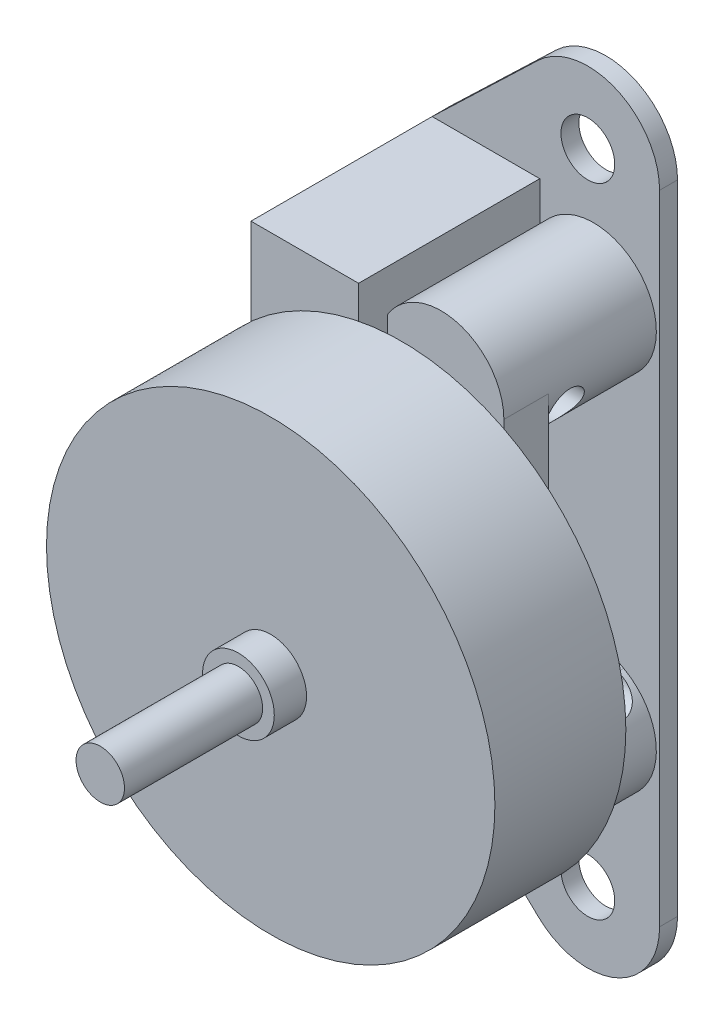
SolidWorks part; units mm, degrees
ref_plane "Front Plane" through (0, 0, 0) normal (0, 0, 1) x (1, 0, 0)
ref_plane "Top Plane" through (0, 0, 0) normal (0, 1, 0) x (1, 0, 0)
ref_plane "Right Plane" through (0, 0, 0) normal (1, 0, 0) x (0, 0, -1)
sketch "Sketch1" plane through (0, 0, 0) normal (0, 0, 1) x (1, 0, 0)
  line L0 (47.18, 17.78) -> (47.18, -17.78)
  line L1 (39.18, 17.78) -> (39.18, -17.78)
  circle A0 centre (43.18, 17.78) radius 1.5 construction
  circle A1 centre (43.18, 17.78) radius 1.5
  circle A2 centre (43.18, -17.78) radius 1.5 construction
  circle A3 centre (43.18, -17.78) radius 1.5
  circle A4 centre (43.18, 17.78) radius 4
  circle A5 centre (43.18, -17.78) radius 4
  point P12 (47.18, -17.78)
  dimension "D1" = 8
extrude "Boss-Extrude1" add sketch "Sketch1" along normal blind 1 contours A5 L0 A4 L1 | A4 A1 | A5 A3 region at (43.18, 13.8931, 0) region at (43.18, 0, 0) region at (43.18, -21.6669, 0)
sketch "Sketch2" plane through (0, 0, 1) normal (0, 0, 1) x (1, 0, 0)
  line L0 (40.4119, 20.6675) -> (34.5, 15)
  line L1 (34.5, 15) -> (34.5, -15)
  line L2 (34.5, -15) -> (40.4119, -20.6675)
  line L3 (39.18, 17.78) -> (39.18, -17.78) construction
  line L4 (39.18, 17.78) -> (39.18, -17.78)
  line L5 (48.5, -24.75) -> (48.5, 24.75) construction
  line L7 (34.5, 0) -> (39.18, 0) construction
  arc A0 (47.18, 17.78) -> (39.18, 17.78) centre (43.18, 17.78) ccw construction
  arc A1 (39.18, -17.78) -> (47.18, -17.78) centre (43.18, -17.78) ccw construction
  arc A2 (47.18, 17.78) -> (39.18, 17.78) centre (43.18, 17.78) ccw
  arc A3 (39.18, -17.78) -> (47.18, -17.78) centre (43.18, -17.78) ccw
  line M1 (39.18, 17.78) -> (39.18, -17.78)
  arc M2 (39.18, -17.78) -> (47.18, -17.78) centre (43.18, -17.78) ccw
  arc M4 (47.18, 17.78) -> (39.18, 17.78) centre (43.18, 17.78) ccw
  dimension "D1" = 14
  dimension "D2" = 30
extrude "Boss-Extrude2" add sketch "Sketch2" against normal blind 1 contours L1 L7 L0 M1 M4 | L7 L1 L2 L4 M2 region at (36.953, 8.7197, 1) region at (36.953, -8.7197, 1)
sketch "Sketch3" plane through (0, 0, 1) normal (0, 0, 1) x (1, 0, 0)
  line L0 (34.5, 15) -> (34.5, 11.5) construction
  line L1 (34.5, 15) -> (40.5, 15)
  line L2 (34.5, 15) -> (34.5, 6.75)
  line L3 (34.5, 6.75) -> (40.5, 6.75)
  line L4 (40.5, 15) -> (40.5, 6.75)
  line L5 (34.5, -15) -> (40.5, -15)
  line L6 (34.5, -15) -> (34.5, -3.75)
  line L7 (34.5, -3.75) -> (40.5, -3.75)
  line L8 (40.5, -15) -> (40.5, -3.75)
  line L9 (34.5, 11.5) -> (59.3702, 11.5) construction
  line L10 (34.5, -15) -> (34.5, -11.5) construction
  line L11 (34.5, -11.5) -> (58.5732, -11.5) construction
  line L12 (43.18, 17.78) -> (43.18, 11.5) construction
  line L13 (43.18, -17.78) -> (43.18, -11.5) construction
  dimension "D1" = 10.5
  dimension "D2" = 23
  dimension "D3" = 7.75
  dimension "D4" = 4.75
  dimension "D5" = 6
extrude "Boss-Extrude3" add sketch "Sketch3" along normal blind 7.1
sketch "Sketch4" plane through (0, 0, 1) normal (0, 0, 1) x (1, 0, 0)
  line L0 (37.5, 6.75) -> (37.5, -3.75) construction
  line L1 (34.5, 6.75) -> (40.5, 6.75) construction
  line L2 (40.5, -3.75) -> (34.5, -3.75) construction
  line L3 (37.5, 1.5) -> (43.5, 1.5) construction
  line L4 (34.5, 6.75) -> (34.5, -3.75) construction
  line L5 (40.5, 10.875) -> (56.47, 10.875) construction
  line L6 (40.5, 6.75) -> (40.5, 15) construction
  line L7 (40.5, -9.375) -> (56.47, -9.375) construction
  line L8 (40.5, -15) -> (40.5, -3.75) construction
  line L9 (43.5, 1.5) -> (43.5, -9.375) construction
  line L10 (43.5, 1.5) -> (43.5, 10.875) construction
  circle A0 centre (43.5, 1.5) radius 2.1
  circle A1 centre (43.5, 10.875) radius 3.5
  circle A2 centre (43.5, -9.375) radius 3.5
  line M3 (40.5, -3.75) -> (40.5, -15)
  line M11 (40.5, 15) -> (40.5, 6.75)
  dimension "D2" = 4.2
  dimension "D3" = 7
  dimension "D1" = 9
extrude "Boss-Extrude4" add sketch "Sketch4" along normal blind 6 contours A1 M11 | A2 M3 region at (43.6048, 10.875, 1) region at (43.6048, -9.375, 1)
sketch "Sketch5" plane through (0, 0, 7) normal (0, 0, 1) x (1, 0, 0)
  line L0 (47, 10.875) -> (47, -9.375)
  line L1 (40, 10.875) -> (40, -9.375)
  arc A0 (40.5, 9.0722) -> (40.5, 12.6778) centre (43.5, 10.875) ccw construction
  circle A1 centre (43.5, 10.875) radius 3.5
  arc A2 (40.5, -11.1778) -> (40.5, -7.5722) centre (43.5, -9.375) ccw construction
  circle A3 centre (43.5, -9.375) radius 3.5
  line M3 (40.5, 12.6778) -> (40.5, 9.0722)
  arc M4 (40.5, 9.0722) -> (40.5, 12.6778) centre (43.5, 10.875) ccw
extrude "Boss-Extrude5" add sketch "Sketch5" along normal blind 1.5 contours M4 M3 | A3 L0 A1 L1 M4 | A3 region at (43.6048, 10.875, 7) region at (43.5, 0.75, 7) region at (43.5, -9.375, 7)
extrude "Cut-Extrude1" cut sketch "Sketch4<3>" along normal blind 12 contours A0 region at (43.5, 1.5, 1)
sketch "Sketch4<3>" plane through (0, 0, 1) normal (0, 0, 1) x (1, 0, 0) same geometry as "Sketch4"
sketch "Sketch6" plane through (34.5, 0, 0) normal (-1, 0, 0) x (0, 0, 1)
  line L0 (8.1, 15) -> (8.1, 6.75) construction
  line L1 (8.1, 11.5) -> (0, 11.5) construction
  line L2 (8.1, 11.5) -> (8.1, -11.5) construction
  line L3 (8.1, -11.5) -> (0, -11.5) construction
  line L4 (0, 11.5) -> (0, -11.5) construction
  line L5 (0, 15) -> (0, -15) construction
  line L6 (8.1, -3.75) -> (8.1, -15) construction
  line L8 (0, 0) -> (8.1, 0) construction
  circle A0 centre (5.8, 9.5) radius 1
  circle A1 centre (2.3, -6.5) radius 1
  point P8 (0, 0)
  dimension "D2" = 16
  dimension "D3" = 2
  dimension "D1" = 23
  dimension "D4" = 2.3
  dimension "D5" = 2.3
  dimension "D6" = 2
  dimension "D7" = 5
extrude "Cut-Extrude2" cut sketch "Sketch6" against normal blind 13
sketch "Sketch7" plane through (0, 0, 8.5) normal (0, 0, 1) x (1, 0, 0)
  circle A0 centre (43.5, 1.5) radius 3.7
  dimension "D1" = 7.4
extrude "Boss-Extrude6" add sketch "Sketch7" along normal blind 3.2 separate body
sketch "Sketch8" plane through (0, 0, 11.7) normal (0, 0, 1) x (1, 0, 0)
  circle A0 centre (43.5, 1.5) radius 12.5
  dimension "D1" = 25
extrude "Boss-Extrude7" add sketch "Sketch8" along normal blind 7.3
sketch "Sketch9" plane through (0, 0, 19) normal (0, 0, 1) x (1, 0, 0)
  circle A0 centre (43.5, 1.5) radius 2
  dimension "D1" = 4
extrude "Boss-Extrude8" add sketch "Sketch9" along normal blind 1.8
sketch "Sketch10" plane through (0, 0, 20.8) normal (0, 0, 1) x (1, 0, 0)
  circle A0 centre (43.5, 1.5) radius 1.35
  dimension "D1" = 2.7
extrude "Boss-Extrude9" add sketch "Sketch10" along normal blind 7.7
sketch "Sketch11" plane through (0, 0, 8.1) normal (0, 0, 1) x (1, 0, 0)
  line L1 (40, 6.75) -> (40.5, 6.75)
  line L2 (40, 6.75) -> (40, 15)
  line L3 (40, 15) -> (40.5, 15)
  line L4 (34.5, 15) -> (34.5, 6.75)
  line L5 (34.5, 6.75) -> (40, 6.75)
  line L6 (40.5, 12.6778) -> (40.5, 15)
  line L7 (40.5, 15) -> (34.5, 15)
  line L8 (34.5, 15) -> (34.5, 6.75)
  line L9 (34.5, 6.75) -> (40, 6.75)
  line L10 (40.5, 12.6778) -> (40.5, 15)
  line L11 (40.5, 15) -> (34.5, 15)
  line L12 (34.5, -3.75) -> (34.5, -15)
  line L13 (34.5, -15) -> (40.5, -15)
  line L14 (40.5, -15) -> (40.5, -11.1778)
  line L15 (40, -3.75) -> (34.5, -3.75)
  line L16 (34.5, -3.75) -> (34.5, -15)
  line L17 (34.5, -15) -> (40.5, -15)
  line L18 (40.5, -15) -> (40.5, -11.1778)
  line L19 (40, -3.75) -> (34.5, -3.75)
  line L20 (40.5, 6.75) -> (40.5, 15)
  line L21 (40, -9.375) -> (40, -3.75)
  line L22 (40.5, 9.0722) -> (40.5, 12.6778)
  line L23 (40.5, 9.0722) -> (40.5, 12.6778)
  line L24 (40, 6.75) -> (40, 10.875)
  line L25 (40, 6.75) -> (40, 10.875)
  line L26 (40, -9.375) -> (40, -3.75)
  line L27 (40.5, -15) -> (40, -15)
  line L28 (40.5, -15) -> (40.5, -3.75)
  line L29 (40.5, -3.75) -> (40, -3.75)
  line L30 (40, -15) -> (40, -3.75)
  arc A1 (40, 10.875) -> (40.5, 9.0722) centre (43.5, 10.875) ccw
  arc A2 (40, 10.875) -> (40.5, 9.0722) centre (43.5, 10.875) ccw
  arc A3 (40, -9.375) -> (40.5, -11.1778) centre (43.5, -9.375) ccw
  arc A4 (40, -9.375) -> (40.5, -11.1778) centre (43.5, -9.375) ccw
  line M9 (34.5, 15) -> (34.5, 6.75)
  line M10 (34.5, 6.75) -> (40, 6.75)
  line M11 (40.5, 12.6778) -> (40.5, 15)
  line M12 (40.5, 15) -> (34.5, 15)
  arc M13 (40, 10.875) -> (40.5, 9.0722) centre (43.5, 10.875) ccw
  line M14 (40.5, 9.0722) -> (40.5, 12.6778)
  line M15 (40, 6.75) -> (40, 10.875)
  dimension "D1" = 0
  dimension "D2" = 0
extrude "Boss-Extrude10" add sketch "Sketch11" along normal blind 2 contours L17 L30 L26 L19 L16 | A4 L30 L17 L18 | L26 A4 L28 L29 | L2 M15 M12 M9 M10 | L1 L20 M13 M15 | L2 M13 M14 M11 M12 region at (40.2295, 8.2331, 8.1) region at (37.25, 10.875, 8.1) region at (40.2611, 12.3108, 8.1) region at (37.25, -9.375, 8.1) region at (40.2587, -7.1856, 8.1) region at (40.2365, -12.7774, 8.1)
sketch "Sketch13" plane through (0, 0, 1) normal (0, 0, 1) x (1, 0, 0)
  line L0 (34.5, 6.75) -> (40.5, 6.75) construction
  line L1 (34.5, 6.75) -> (40.5, 6.75)
  line L2 (40.5, -3.75) -> (34.5, -3.75) construction
  line L3 (40.5, -3.75) -> (34.5, -3.75)
  line L4 (40.5, 12.6778) -> (40.5, 6.75) construction
  line L5 (40.5, 6.75) -> (44.1464, 7.4352)
  line L6 (40.5, -3.75) -> (45.1769, -6.3029)
  line L7 (40.5, -3.75) -> (40.5, -11.1778) construction
  line L8 (40.5, -3.75) -> (40.5, -11.1778)
  line L9 (40.5, 12.6778) -> (40.5, 6.75)
  arc A0 (47, 10.875) -> (40.5, 12.6778) centre (43.5, 10.875) ccw construction
  arc A1 (40.5, 9.0722) -> (40.5, 12.6778) centre (43.5, 10.875) ccw
  arc A2 (40.5, -11.1778) -> (40.5, -7.5722) centre (43.5, -9.375) ccw construction
  arc A3 (40.5, -11.1778) -> (40.5, -7.5722) centre (43.5, -9.375) ccw
  line M4 (40.5, -3.75) -> (40.5, -7.5722)
  arc M5 (40.5, -7.5722) -> (40.5, -11.1778) centre (43.5, -9.375) cw
  arc M15 (40.5, 12.6778) -> (40.5, 9.0722) centre (43.5, 10.875) cw
  line M16 (40.5, 9.0722) -> (40.5, 6.75)
extrude "Boss-Extrude11" add sketch "Sketch13" along normal up to surface (6 mm away) contours L6 M4 M5 | L5 M16 M15 region at (41.3764, 7.5705, 1) region at (41.6732, -5.4861, 1) up to face at (45.6, 1.5, 7)
sketch "Sketch14" plane through (34.5, 0, 0) normal (-1, 0, 0) x (0, 0, 1)
  circle A0 centre (5.8, 9.5) radius 1 construction
  circle A1 centre (5.8, 9.5) radius 1
  circle A2 centre (2.3, -6.5) radius 1 construction
  circle A3 centre (2.3, -6.5) radius 1
extrude "Cut-Extrude3" cut sketch "Sketch14" against normal through all
sketch "Sketch15" plane through (0, 0, 8.5) normal (0, 0, 1) x (1, 0, 0)
  line L0 (40, 6.75) -> (40, -3.75) construction
  line L1 (40, 6.75) -> (40, -3.75)
  circle A0 centre (43.5, 1.5) radius 5
  dimension "D1" = 10
extrude "Boss-Extrude12" add sketch "Sketch15" against normal up to surface (1.5 mm away) contours L1 A0 region at (39.3915, 1.5, 8.5) up to face at (45.6, 1.5, 7)
sketch "Sketch16" plane through (0, 0, 7) normal (0, 0, -1) x (-1, 0, 0)
  circle A0 centre (-43.5, 1.5) radius 2.1 construction
  circle A1 centre (-43.5, 1.5) radius 2.1
extrude "Boss-Extrude13" add sketch "Sketch16" against normal blind 0.2
sketch "Sketch17" plane through (0, 0, 8.5) normal (0, 0, 1) x (1, 0, 0)
  line L7 (40.5, 12.6778) -> (40.5, 6.75)
  line L8 (40.5, 6.75) -> (40, 6.75)
  line L9 (40, 6.75) -> (40, 5.0707)
  line L10 (40, -2.0707) -> (40, -3.75)
  line L11 (40, -3.75) -> (40.5, -3.75)
  line L12 (40.5, -3.75) -> (40.5, -11.1778)
  line L13 (47, -9.375) -> (47, 10.875)
  line L14 (40.5, 12.6778) -> (40.5, 6.75)
  line L15 (40.5, 6.75) -> (40, 6.75)
  line L16 (40, 6.75) -> (40, 5.0707)
  line L17 (40, -2.0707) -> (40, -3.75)
  line L18 (40, -3.75) -> (40.5, -3.75)
  line L19 (40.5, -3.75) -> (40.5, -11.1778)
  line L20 (47, -9.375) -> (47, 10.875)
  circle A0 centre (43.5, 1.5) radius 2.1 construction
  circle A1 centre (43.5, 1.5) radius 2.1
  arc A3 (40, 5.0707) -> (40, -2.0707) centre (43.5, 1.5) ccw
  arc A4 (40.5, -11.1778) -> (47, -9.375) centre (43.5, -9.375) ccw
  arc A5 (47, 10.875) -> (40.5, 12.6778) centre (43.5, 10.875) ccw
  arc A6 (40, 5.0707) -> (40, -2.0707) centre (43.5, 1.5) ccw
  arc A7 (40.5, -11.1778) -> (47, -9.375) centre (43.5, -9.375) ccw
  arc A8 (47, 10.875) -> (40.5, 12.6778) centre (43.5, 10.875) ccw
  dimension "D1" = 0
extrude "Boss-Extrude14" add sketch "Sketch17" along normal blind 1
sketch "Sketch18" plane through (0, 0, 10.1) normal (0, 0, 1) x (1, 0, 0)
  line L4 (40.5, -15) -> (40.5, -3.75)
  line L5 (40.5, -3.75) -> (34.5, -3.75)
  line L6 (34.5, -3.75) -> (34.5, -15)
  line L7 (34.5, -15) -> (40.5, -15)
  line L8 (40.5, -15) -> (40.5, -3.75)
  line L9 (40.5, -3.75) -> (34.5, -3.75)
  line L10 (34.5, -3.75) -> (34.5, -15)
  line L11 (34.5, -15) -> (40.5, -15)
  line L12 (40.5, 6.75) -> (40.5, 15)
  line L13 (40.5, 15) -> (34.5, 15)
  line L14 (34.5, 15) -> (34.5, 6.75)
  line L15 (34.5, 6.75) -> (40.5, 6.75)
  line L16 (40.5, 6.75) -> (40.5, 15)
  line L17 (40.5, 15) -> (34.5, 15)
  line L18 (34.5, 15) -> (34.5, 6.75)
  line L19 (34.5, 6.75) -> (40.5, 6.75)
  dimension "D1" = 0
  dimension "D2" = 0
extrude "Boss-Extrude15" add sketch "Sketch18" along normal blind 1
